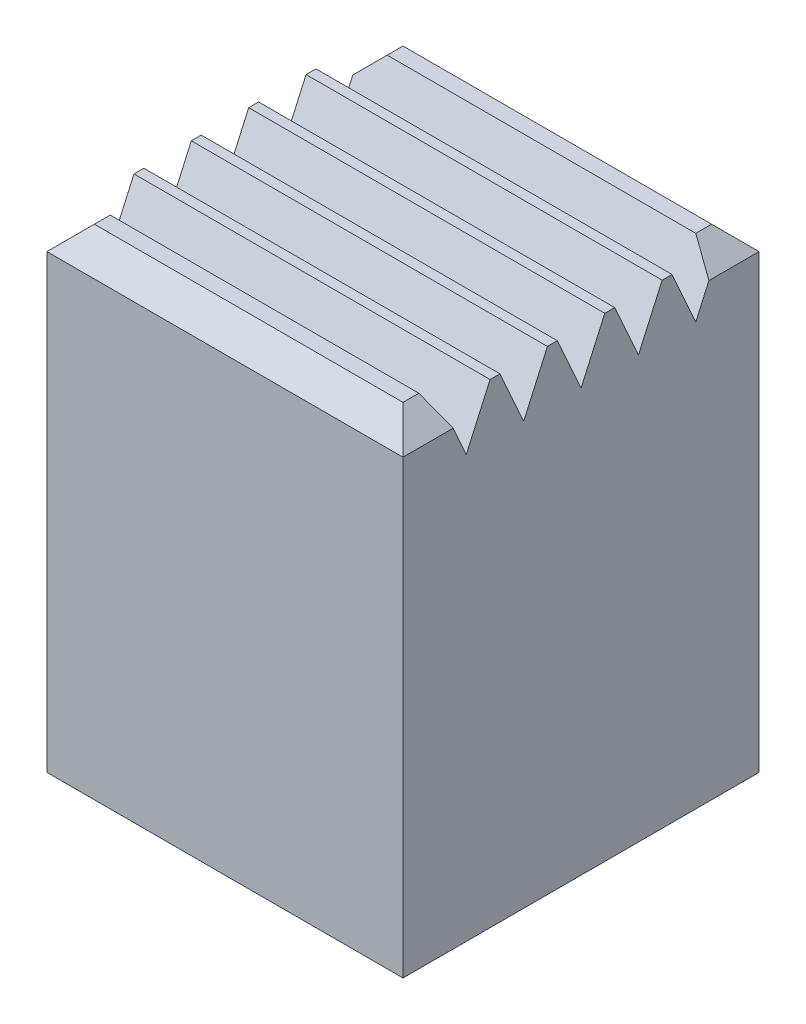
SolidWorks part; units mm, degrees
ref_plane "Front Plane" through (0, 0, 0) normal (0, 0, 1) x (1, 0, 0)
ref_plane "Top Plane" through (0, 0, 0) normal (0, 1, 0) x (1, 0, 0)
ref_plane "Right Plane" through (0, 0, 0) normal (1, 0, 0) x (0, 0, -1)
sketch "Sketch1" plane through (0, 0, 0) normal (0, 1, 0) x (1, 0, 0)
  line L1 (0, 0) -> (4.5, 0)
  line L2 (0, 0) -> (0, 4.5)
  line L3 (0, 4.5) -> (4.5, 4.5)
  line L4 (4.5, 0) -> (4.5, 4.5)
  dimension "D1" = 4.5
extrude "Boss-Extrude1" add sketch "Sketch1" along normal blind 6
sketch "Sketch2" plane through (0, 0, 0) normal (0, -1, 0) x (1, 0, 0)
  line L0 (2.25, -0.65) -> (2.25, 0) construction
  line L1 (0.65, -0.65) -> (3.85, -0.65)
  line L2 (0.65, -0.65) -> (0.65, -3.85)
  line L3 (0.65, -3.85) -> (3.85, -3.85)
  line L4 (3.85, -0.65) -> (3.85, -3.85)
  line L5 (0, 0) -> (4.5, 0) construction
  line L6 (0.65, -2.25) -> (0, -2.25) construction
  line L7 (0, -4.5) -> (0, 0) construction
  dimension "D1" = 3.2
extrude "Cut-Extrude1" cut sketch "Sketch2" against normal blind 4.9
sketch "Sketch3" plane through (0, 0, 0) normal (-1, 0, 0) x (0, 0, 1)
  line L0 (-4, 6) -> (-3.7, 5.33)
  line L1 (-4.5, 6) -> (0, 6) construction
  line L2 (-3.7, 5.33) -> (-3.4, 6)
  line L3 (-4, 6) -> (-3.4, 6)
  dimension "D1" = 0.5
  dimension "D2" = 0.6
  dimension "D3" = 0.67
extrude "Cut-Extrude2" cut sketch "Sketch3" against normal up to surface (4.5 mm away) contours L3 L2 L0 up to face at (4.5, 3, -2.25)
pattern_linear "LPattern1" count 5 spacing 0.725 along (0, 0, 1) of "Cut-Extrude2"
chamfer "Chamfer1" distance 0.3 angle 45 6 edges at (4.5, 6, -0.25) (2.25, 6, 0) (0, 6, -0.25) (0, 6, -4.25) (2.25, 6, -4.5) (4.5, 6, -4.25)
